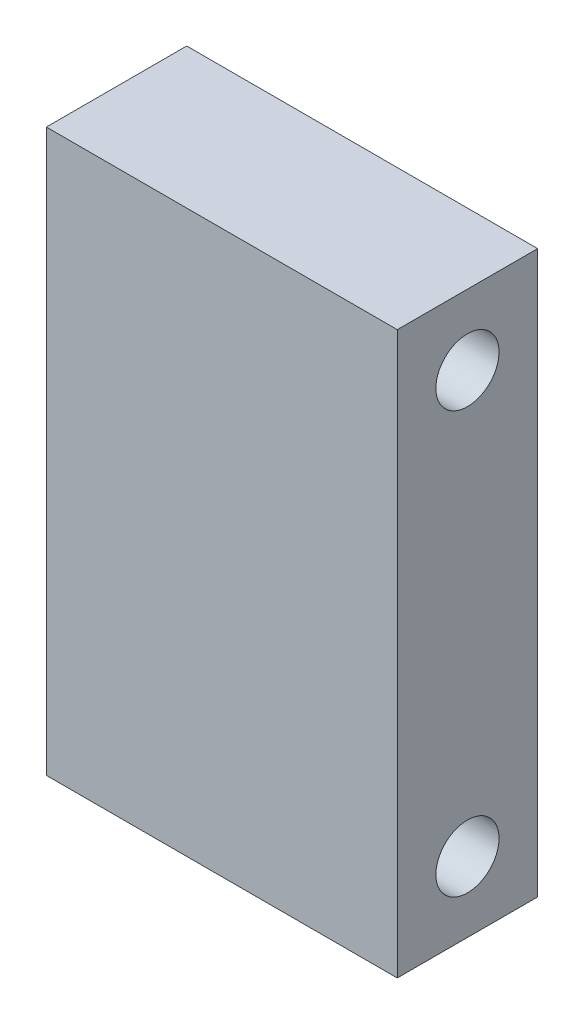
SolidWorks part; units mm, degrees
material "PA6 (3.1325)"
ref_plane "Płaszczyzna przednia" through (0, 0, 0) normal (0, 0, 1) x (1, 0, 0)
ref_plane "Płaszczyzna górna" through (0, 0, 0) normal (0, 1, 0) x (1, 0, 0)
ref_plane "Płaszczyzna prawa" through (0, 0, 0) normal (1, 0, 0) x (0, 0, -1)
sketch "Szkic1" plane through (0, 0, 0) normal (0, 0, 1) x (1, 0, 0)
  line L1 (25, -40) -> (-25, -40)
  line L2 (25, -40) -> (25, 40)
  line L3 (25, 40) -> (-25, 40)
  line L4 (-25, -40) -> (-25, 40)
  line L5 (25, -40) -> (-25, 40) construction
  line L6 (25, 40) -> (-25, -40) construction
  point P0 (0, 0)
  dimension "D1" = 50
  dimension "D2" = 80
extrude "Dodanie-wyciągnięcie1" add sketch "Szkic1" along normal mid plane 20
hole_wizard "Otwór pod śrubę M81" positions "Szkic2" profile "Szkic3" hole size "M8" standard "DIN" end condition up to next
sketch "Szkic2" plane through (-25, 0, 0) normal (-1, 0, 0) x (0, 0, 1)
  line L0 (0, 30) -> (0, -30) construction
  point P0 (0, 30)
  point P2 (0, -30)
  dimension "D1" = 60
sketch "Szkic3" plane through (-25, 30, 0) normal (0, 1, 0) x (0, 0, 1)
  line L0 (0, 0) -> (0, 50)
  line L1 (0, 50) -> (4.5, 50)
  line L2 (4.5, 50) -> (4.5, 0)
  line L5 (4.5, 0) -> (0, 0)
  line L11 (0, -6.35) -> (0, 107.95) construction
  dimension "Średnica otworu na wylot" = 9
  dimension "Głębokość otworu na wylot" = 50
